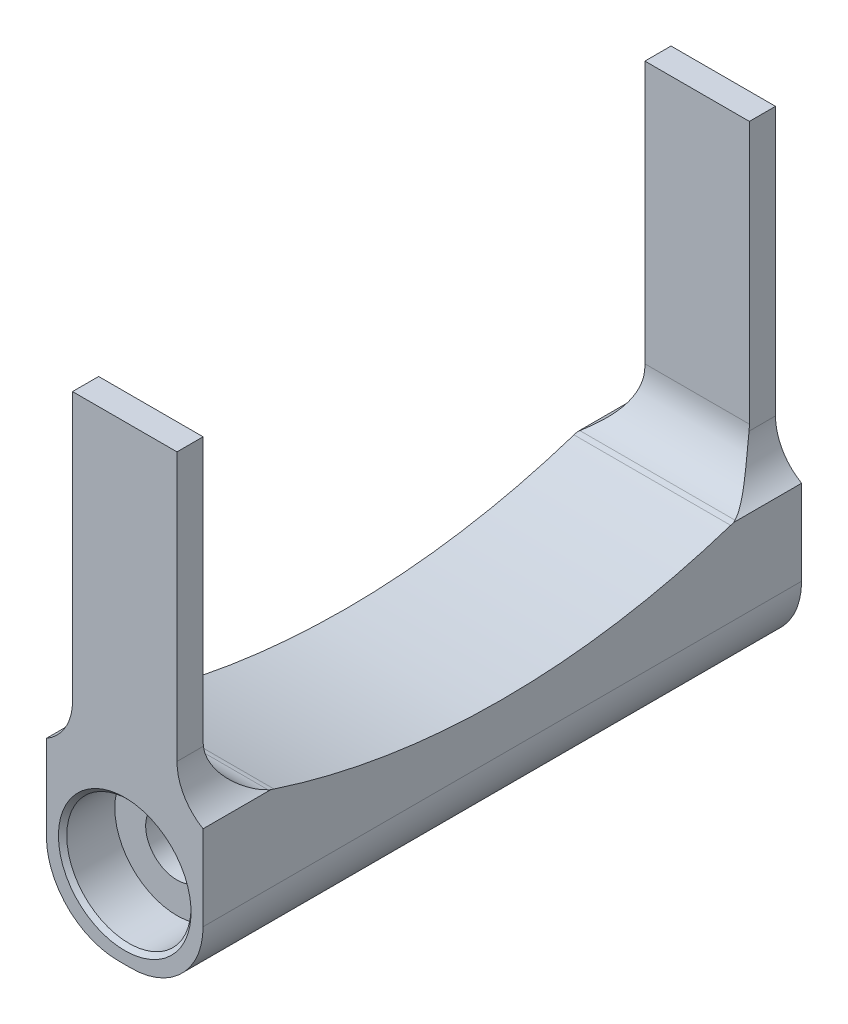
SolidWorks part; units mm, degrees
material "PLA"
ref_plane "Front Plane" through (0, 0, 0) normal (0, 0, 1) x (1, 0, 0)
ref_plane "Top Plane" through (0, 0, 0) normal (0, 1, 0) x (1, 0, 0)
ref_plane "Right Plane" through (0, 0, 0) normal (1, 0, 0) x (0, 0, -1)
sketch "Sketch10" plane through (0, 0, 0) normal (0, 0, 1) x (1, 0, 0)
  line L1 (-15, -15) -> (15, -15)
  line L2 (-15, -15) -> (-15, 15)
  line L3 (-15, 15) -> (15, 15)
  line L4 (15, -15) -> (15, 15)
  line L5 (-15, -15) -> (15, 15) construction
  line L6 (-15, 15) -> (15, -15) construction
  circle A0 centre (0, 0) radius 6
  dimension "D1" = 12
  dimension "D2" = 30
  dimension "D3" = 30
extrude "Boss-Extrude5" add sketch "Sketch10" along normal blind 114.6
sketch "Sketch12" plane through (15, 0, 0) normal (1, 0, 0) x (0, 0, -1)
  line L0 (-114.6, 15) -> (0, 15) construction
  line L1 (-114.6, -15) -> (-114.6, 15) construction
  line L2 (0, -15) -> (0, 15) construction
  arc A0 (-101.6, 15) -> (-13, 15) centre (-57.3, 147.8063) ccw
  dimension "D3" = 140
  dimension "D1" = 13
  dimension "D2" = 13
extrude "Cut-Extrude3" cut sketch "Sketch12" against normal through all and the other way through all
sketch "Sketch13" plane through (0, 15, 0) normal (0, 1, 0) x (1, 0, 0)
  line L0 (15, 0) -> (-15, 0) construction
  line L1 (-10, 0) -> (10, 0)
  line L2 (-10, 0) -> (-10, -5)
  line L3 (-10, -5) -> (10, -5)
  line L4 (10, 0) -> (10, -5)
  dimension "D1" = 5
  dimension "D2" = 20
extrude "Boss-Extrude6" add sketch "Sketch13" along normal blind 60
fillet "Fillet3" radius 10 3 edges at (-10, 15, 2.5) (0, 15, 5) (10, 15, 2.5)
ref_plane "Plane3" through (0, 0, 57.3) normal (0, 0, -1) x (-1, 0, 0)
mirror "Mirror1" about plane through (0, 0, 57.3) normal (0, 0, -1) of "Boss-Extrude6", "Fillet3"
fillet "Fillet4" radius 13.75 2 edges at (15, -15, 57.3) (-15, -15, 57.3)
sketch "Sketch14" plane through (0, 0, 0) normal (0, 0, -1) x (-1, 0, 0)
  circle A0 centre (0, 0) radius 11.9
  dimension "D1" = 23.8
extrude "Cut-Extrude4" cut sketch "Sketch14" against normal blind 10
mirror "Mirror2" about plane through (0, 0, 57.3) normal (0, 0, -1) of "Cut-Extrude4"
fillet "Fillet5" radius 13.75 2 edges at (0, 15, 101.6) (0, 15, 13)
chamfer "Chamfer1" distance 0.8 angle 45 1 edges at (-11.9, 0, 114.6)
chamfer "Chamfer2" distance 0.8 angle 45 1 edges at (-11.9, 0, 0)
